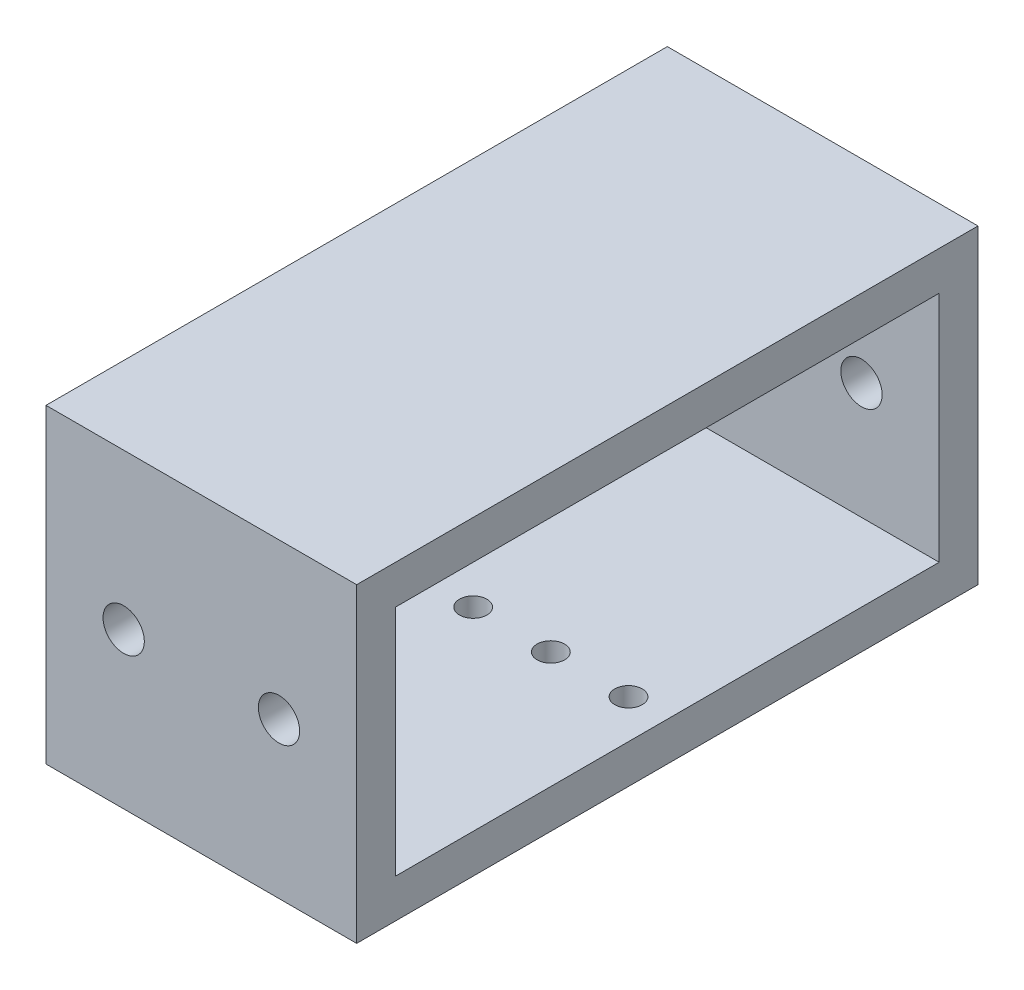
SolidWorks part; units mm, degrees
ref_plane "Front Plane" through (0, 0, 0) normal (0, 0, 1) x (1, 0, 0)
ref_plane "Top Plane" through (0, 0, 0) normal (0, 1, 0) x (1, 0, 0)
ref_plane "Right Plane" through (0, 0, 0) normal (1, 0, 0) x (0, 0, -1)
sketch "Sketch2" plane through (0, 0, 0) normal (1, 0, 0) x (0, 0, -1)
  line L9 (-50.8, -25.4) -> (50.8, -25.4)
  line L10 (-50.8, -25.4) -> (-50.8, 25.4)
  line L11 (-50.8, 25.4) -> (50.8, 25.4)
  line L12 (50.8, -25.4) -> (50.8, 25.4)
  line L13 (-50.8, -25.4) -> (50.8, 25.4) construction
  line L14 (-50.8, 25.4) -> (50.8, -25.4) construction
  line L15 (-44.45, -19.05) -> (44.45, -19.05)
  line L16 (-44.45, -19.05) -> (-44.45, 19.05)
  line L17 (-44.45, 19.05) -> (44.45, 19.05)
  line L18 (44.45, -19.05) -> (44.45, 19.05)
  line L19 (-44.45, -19.05) -> (44.45, 19.05) construction
  line L20 (-44.45, 19.05) -> (44.45, -19.05) construction
  point P0 (0, 0)
  point P5 (0, 0)
  dimension "D1" = 6.35
  dimension "D2" = 101.6
  dimension "D3" = 50.8
  dimension "D4" = 6.35
extrude "Boss-Extrude1" add sketch "Sketch2" along normal mid plane 50.8
sketch "Sketch3" plane through (0, 0, 50.8) normal (0, 0, 1) x (1, 0, 0)
  line L0 (-12.7, 0) -> (12.7, 0)
  point P4 (0, 0)
  dimension "D1" = 25.4
hole_wizard "1/4 Clearance Hole1" positions "Sketch4" profile "Sketch5" hole size "1/4" standard "ANSI Inch" end condition through all
sketch "Sketch4" plane through (0, 0, 50.8) normal (0, 0, 1) x (1, 0, 0)
  point P0 (-12.7, 0)
  point P3 (12.7, 0)
sketch "Sketch5" plane through (-12.7, 0, 50.8) normal (1, 0, 0) x (0, -1, 0)
  line L0 (0, 0) -> (0, 101.6)
  line L1 (0, 101.6) -> (3.3782, 101.6)
  line L2 (3.3782, 101.6) -> (3.3782, 0)
  line L5 (3.3782, 0) -> (0, 0)
  line L11 (0, -6.35) -> (0, 107.95) construction
  dimension "Thru Hole Dia." = 6.7564
  dimension "Thru Hole Depth" = 101.6
sketch "Sketch6" plane through (0, -19.05, 0) normal (0, 1, 0) x (1, 0, 0)
  line L0 (25.4, 0) -> (-25.4, 0) construction
  line L1 (25.4, -44.45) -> (25.4, 44.45) construction
  line L2 (-25.4, -44.45) -> (-25.4, 44.45) construction
  line L3 (6.35, 0) -> (19.05, 0)
  point P9 (12.7, 0)
  point P10 (0, 0)
  dimension "D1" = 12.7
  dimension "D2" = 12.7
hole_wizard "#8 Clearance Hole1" positions "Sketch7" profile "Sketch8" hole size "#8" standard "ANSI Inch" end condition through all
sketch "Sketch7" plane through (0, -19.05, 0) normal (0, 1, 0) x (1, 0, 0)
  point P0 (6.35, 0)
  point P3 (19.05, 0)
sketch "Sketch8" plane through (6.35, -19.05, 0) normal (1, 0, 0) x (0, 0, 1)
  line L0 (0, 0) -> (0, 6.35)
  line L1 (0, 6.35) -> (2.2479, 6.35)
  line L2 (2.2479, 6.35) -> (2.2479, 0)
  line L5 (2.2479, 0) -> (0, 0)
  line L11 (0, -6.35) -> (0, 107.95) construction
  dimension "Thru Hole Dia." = 4.4958
  dimension "Thru Hole Depth" = 6.35
mirror "Mirror1" about plane through (0, 0, 0) normal (1, 0, 0) of "#8 Clearance Hole1"
equation "\"wall\"=0.25"
equation "\"D1@Sketch2\"=\"wall\""
equation "\"Width\"=4"
equation "\"D2@Sketch2\"=\"Width\""
equation "\"Height\"=2"
equation "\"D3@Sketch2\"=\"Height\""
equation "\"D4@Sketch2\"=\"wall\""
equation "\"Length\"=2"
equation "\"D1@Boss-Extrude1\"=\"Length\""
equation "\"D2@Sketch6\"=\"Length\"/4"
equation "\"D1@Sketch6\"=\"Length\"/4"
